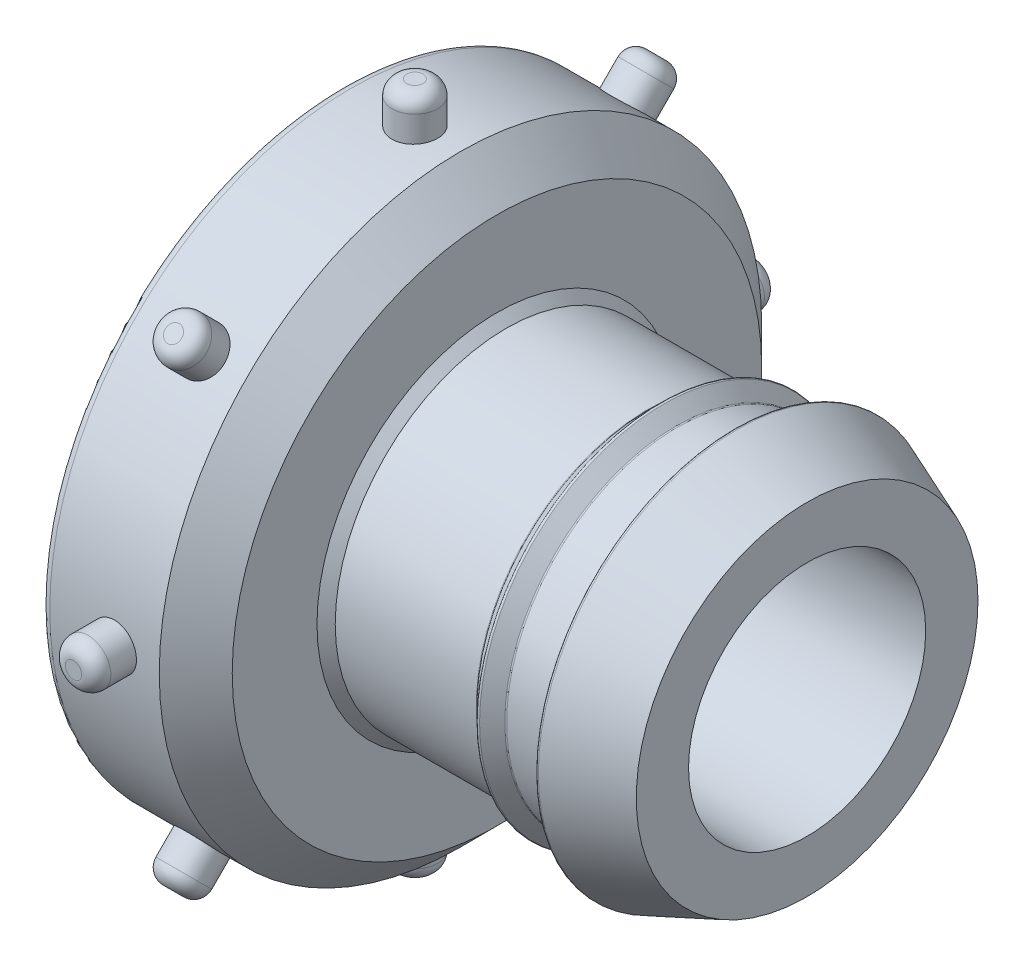
SolidWorks part; units mm, degrees
note: '?' marks a value the reader was unsure of. The reader was unsure of these and kept them because the rebuilt part matched: shared geometry of "Sketch2<3>".
ref_plane "Front Plane" through (0, 0, 0) normal (0, 0, 1) x (1, 0, 0)
ref_plane "Top Plane" through (0, 0, 0) normal (0, 1, 0) x (1, 0, 0)
ref_plane "Right Plane" through (0, 0, 0) normal (1, 0, 0) x (0, 0, -1)
sketch "Sketch1" plane through (0, 0, 0) normal (0, 1, 0) x (1, 0, 0)
  line L0 (0, 0) -> (-17, 0)
  line L1 (0, 0) -> (0, 9.365)
  line L2 (0, 9.365) -> (-3.97, 10.955)
  line L3 (-3.97, 10.955) -> (-3.97, 9.365)
  line L4 (0, 9.365) -> (-19.3321, 9.365) construction
  line L5 (-3.97, 9.365) -> (-7.15, 9.365)
  line L6 (-7.15, 9.365) -> (-7.94, 10.155)
  line L7 (-7.94, 10.155) -> (-8.73, 9.365)
  line L8 (-8.73, 9.365) -> (-17, 9.365)
  line L9 (-17, 9.365) -> (-17, 0)
  dimension "D1" = 17
  dimension "D2" = 9.365
  dimension "D3" = 1.59
  dimension "D4" = 3.97
  dimension "D5" = 7.94
  dimension "D6" = 0.79
revolve "Revolve1" add sketch "Sketch1" angle 360 about L0
sketch "Sketch2" plane through (-17, 0, 0) normal (-1, 0, 0) x (0, 0, 1)
  circle A0 centre (0, 0) radius 9.365
  circle A1 centre (0, 0) radius 9.365 construction
  circle A2 centre (0, 0) radius 6.5
  circle A3 centre (0, 0) radius 16.51
  circle M3 centre (0, 0) radius 9.365
  dimension "D1" = 13
  dimension "D2" = 33.02
extrude "Boss-Extrude1" add sketch "Sketch2" along normal blind 8.5 contours A3 M3 | A2 M3
ref_axis "Axis1" through (-25.5, -18.161, 0) along (0, 1, 0)?
sketch "Sketch4" plane through (-25.5, 0, 0) normal (-1, 0, 0) x (0, 0, 1)
  line L0 (0, -18.161) -> (0, 18.161) construction
  line L1 (9.09, 6.63) -> (-9.09, 6.63)
  line L2 (9.09, 6.63) -> (9.09, -6.92)
  line L3 (9.09, -6.92) -> (-9.09, -6.92)
  line L4 (-9.09, 6.63) -> (-9.09, -6.92)
  circle A1 centre (0, 0) radius 16.51 construction
  point P6 (0, 6.63)
  dimension "D1" = 18.18
  dimension "D2" = 13.55
  dimension "D3" = 6.92
extrude "Cut-Extrude1" cut sketch "Sketch4" against normal blind 7
sketch "Sketch5" plane through (-25.5, 0, 0) normal (-1, 0, 0) x (0, 0, 1)
  circle A0 centre (0, 0) radius 14.14
  dimension "D1" = 28.28
sketch "Sketch6" plane through (0, 0, 0) normal (0, 0, 1) x (1, 0, 0)
  line L0 (-25.5, 14.14) -> (-25.5, -14.14) construction
  circle A0 centre (-25.5, 14.14) radius 0.9
  point P0 (-25.5, 14.14)
  dimension "D1" = 1.8
ref_axis "Axis2" through (-35.0271, 0, 0) along (1, 0, 0)
revolve "Cut-Revolve1" cut sketch "Sketch6" angle 360 about axis through (-35.0271, 0, 0) along (1, 0, 0)
fillet "Fillet1" radius 1 1 edges at (-25.5, 0, -13.24)
ref_plane "Plane1" through (-21.5, 0, 0) normal (-1, 0, 0) x (0, 0, 1)
ref_axis "Axis3" through (-21.5, -18.161, 0) along (0, 1, 0)?
ref_plane "Plane2" through (0, 16.51, 0) normal (0, 1, 0) x (1, 0, 0)
sketch "Sketch7" plane through (0, 16.51, 0) normal (0, 1, 0) x (1, 0, 0)
  circle A0 centre (-21.5, 0) radius 1.25
  dimension "D1" = 2.5
extrude "Boss-Extrude2" add sketch "Sketch7" along normal blind 2.2 and the other way blind 2 contours A0
fillet "Fillet2" radius 0.8 1 edges at (-21.5, 18.71, 1.25)
pattern_circular "CirPattern1" count 8 over 360 about axis through (0, 0, 0) along (1, 0, 0) of "Boss-Extrude2", "Fillet2"
chamfer "Chamfer1" distance 2 angle 45 1 edges at (-17, 0, 16.51)
fillet "Fillet3" radius 0.5 1 edges at (-25.5, 0, 16.51)
fillet "Fillet4" radius 0.1 5 edges at (-8.73, 0, -9.365) (-7.94, 0, -10.155) (-7.15, 0, -9.365) (-3.97, 0, -9.365) (-3.97, 0, -10.955)
chamfer "Chamfer2" distance 0.5 angle 45 1 edges at (-17, 0, 9.365)
extrude "Cut-Extrude2" cut sketch "Sketch2<3>" against normal through all both and the other way through all contours A2
sketch "Sketch2<3>" plane through (-17, 0, 0) normal (-1, 0, 0) x (0, 0, 1) same geometry as "Sketch2"
chamfer "Chamfer3" distance 1 angle 76 1 edges at (-25.5, -6.92, 0)
sketch "Sketch8" plane through (-18.5, 0, 0) normal (-1, 0, 0) x (0, 0, 1)
  line L1 (-9.09, -6.92) -> (-6.5, -6.92)
  line L2 (-9.09, -6.92) -> (-9.09, 0.73)
  line L3 (-9.09, 0.73) -> (-6.5, 0.73)
  line L4 (-6.5, -6.92) -> (-6.5, 0.73)
  circle A0 centre (0, 0) radius 6.5 construction
  dimension "D1" = 7.65
extrude "Boss-Extrude3" add sketch "Sketch8" along normal blind 0.64
fillet "Fillet5" radius 0.5 2 edges at (-19.14, 0.73, -7.795) (-19.14, -3.095, -6.5)
equation "\"WallThick\"= 1.2'thickness of wall for printer"
equation "\"dHole\"= 3.3'diameter of screw hole"
equation "\"D3@Sketch4\"=33.02/2-9.59"
equation "\"D1@Boss-Extrude2\"=(37.42-33.02)/2"
